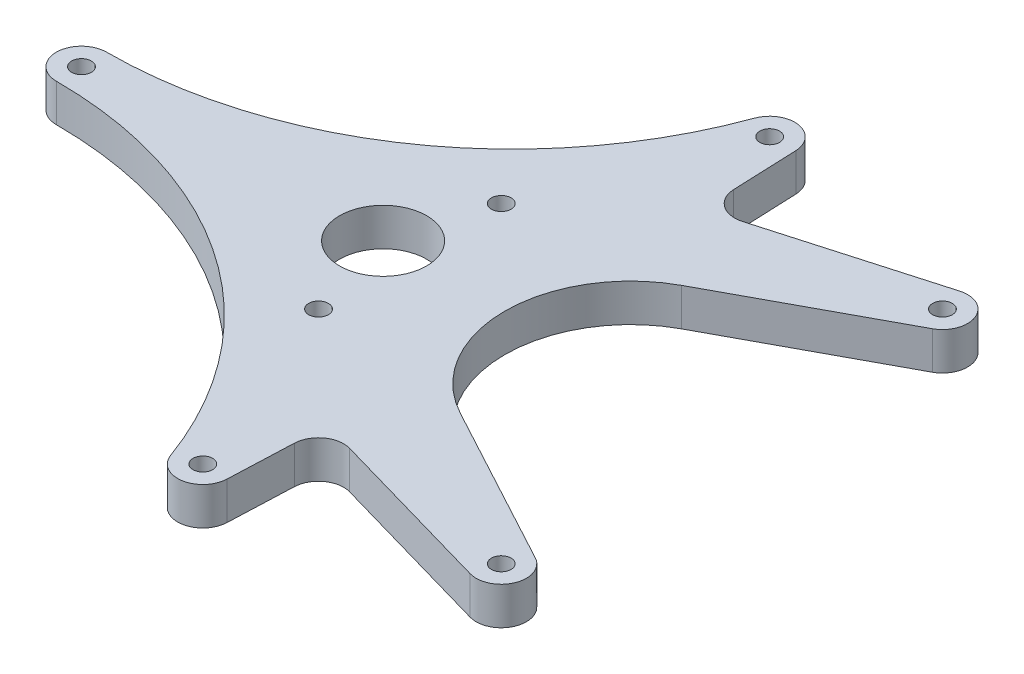
SolidWorks part; units mm, degrees
material "Alloy Steel"
ref_plane "Front Plane" through (0, 0, 0) normal (0, 0, 1) x (1, 0, 0)
ref_plane "Top Plane" through (0, 0, 0) normal (0, 1, 0) x (1, 0, 0)
ref_plane "Right Plane" through (0, 0, 0) normal (1, 0, 0) x (0, 0, -1)
sketch "Sketch2" plane through (0, 0, 0) normal (0, 1, 0) x (1, 0, 0)
  line L2 (62.5, 0) -> (12.5, 0) construction
  line L3 (12.5, 0) -> (0, 0) construction
  line L4 (62.5, 0) -> (179.6744, 0) construction
  line L5 (32.4067, 71.8613) -> (33.0698, 55.4763)
  line L6 (41.1613, -49.628) -> (83.8387, -61.8381)
  line L9 (62.5, 0) -> (85.5854, 55.733) construction
  line L10 (62.5, 0) -> (6.767, 23.0854) construction
  line L11 (0, 0) -> (-76.2, 0) construction
  line L12 (41.1613, 49.628) -> (83.8387, 61.8381)
  line L13 (0, 0) -> (26.0619, 71.6046) construction
  line L14 (32.4067, -71.8613) -> (33.0698, -55.4763)
  line L15 (62.5, 0) -> (39.4146, 55.733) construction
  line L21 (47.4315, 27.9464) -> (88.5991, 50.1438)
  line L22 (47.4315, -27.9464) -> (88.5991, -50.1438)
  arc A0 (47.4315, 27.9464) -> (47.4315, -27.9464) centre (62.5, 0) ccw
  circle A5 centre (26.0619, 71.6046) radius 2.4892
  circle A8 centre (6.767, 23.0854) radius 2.4892
  circle A9 centre (85.5854, 55.733) radius 2.4892
  circle A12 centre (85.5854, -55.733) radius 2.4892
  circle A13 centre (6.767, -23.0854) radius 2.4892
  circle A14 centre (26.0619, -71.6046) radius 2.4892
  circle A16 centre (0, 0) radius 11
  circle A19 centre (26.0619, 71.6046) radius 6.35
  circle A21 centre (85.5854, 55.733) radius 6.35
  circle A22 centre (85.5854, -55.733) radius 6.35
  circle A24 centre (26.0619, -71.6046) radius 6.35
  circle A26 centre (-76.2, 0) radius 2.4892
  circle A27 centre (-76.2, 0) radius 6.35
  arc A28 (-76.2, 6.35) -> (20.0949, 73.7764) centre (-76.2, 108.8249) ccw
  arc A29 (-76.2, -6.35) -> (20.0949, -73.7764) centre (-76.2, -108.8249) cw
  circle A31 centre (6.767, 23.0854) radius 6.35
  circle A32 centre (6.767, -23.0854) radius 6.35
  arc A34 (33.0698, 55.4763) -> (41.1613, 49.628) centre (39.4146, 55.733) ccw
  arc A35 (33.0698, -55.4763) -> (41.1613, -49.628) centre (39.4146, -55.733) cw
  dimension "D2" = 31.75
  dimension "D11" = 76.2
  dimension "D17" = 22
  dimension "D4" = 4.9784
  dimension "D3" = 12.7
  dimension "D10" = 6.35
  dimension "D5" = 50
  dimension "D6" = 12.5
  dimension "D7" = 67.5
  dimension "D8" = 22.5
  dimension "D9" = 45
  dimension "D12" = 60.325
  dimension "D13" = 110
extrude "Boss-Extrude1" add sketch "Sketch2" along normal mid plane 9.525 contours A24 A31 A22 L22 A0 L21 A21 A19 A16 | A19 A5 | A19 | A24 | A24 A14 | A31 A13 | A22 A12 | A21 A9 | A8 | A27 A26 region at (15.2825, 0, 0) region at (32.2311, 0, -71.7294) region at (-71.8369, 0, -4.3631) region at (89.3003, 0, -60.6598) region at (24.9905, 0, 65.5279) region at (90.8837, 0, 52.5704) region at (0.5966, 0, -23.0854) region at (0.5966, 0, 23.0854)
ref_axis "Turbine Axis" through (0, 55, 0) along (0, -1, 0)
ref_axis "Pump Axis" through (62.5, 4.7625, 0) along (0, -1, 0)
